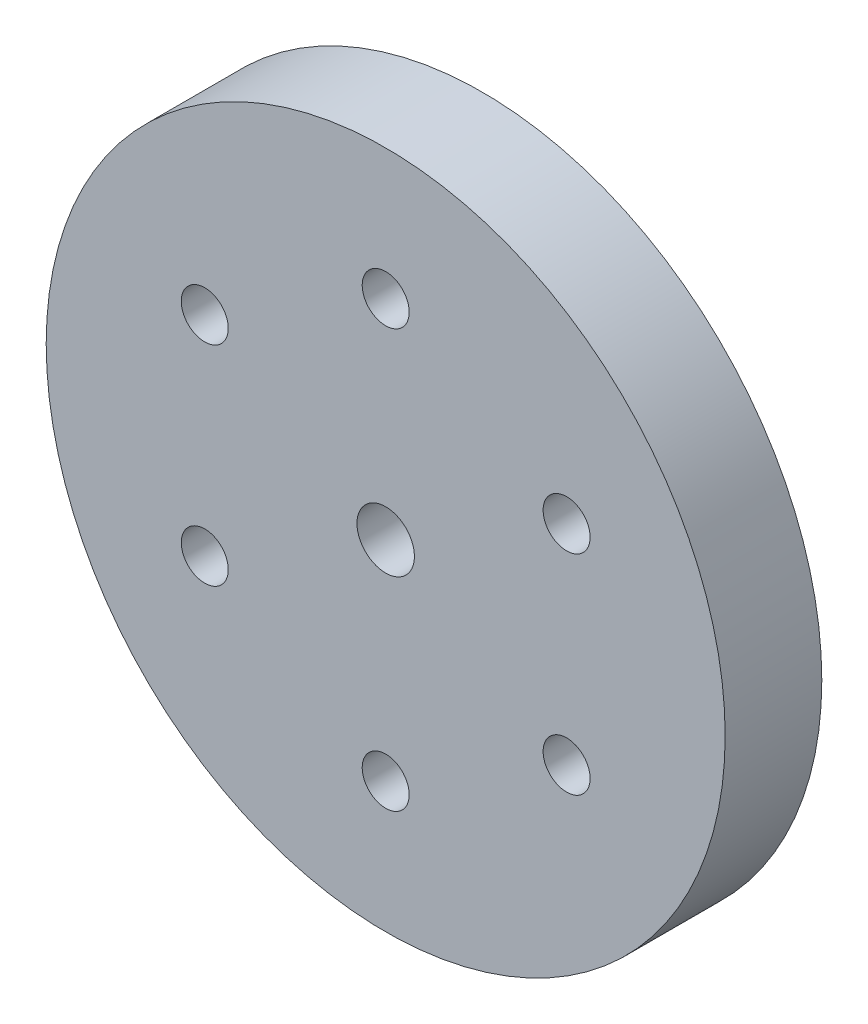
SolidWorks part; units mm, degrees
ref_plane "前视基准面" through (0, 0, 0) normal (0, 0, 1) x (1, 0, 0)
ref_plane "上视基准面" through (0, 0, 0) normal (0, 1, 0) x (1, 0, 0)
ref_plane "右视基准面" through (0, 0, 0) normal (1, 0, 0) x (0, 0, -1)
other "Configuration Table"
sketch "草图1" plane through (0, 0, 0) normal (0, 0, 1) x (1, 0, 0)
  circle A0 centre (0, 0) radius 13
  dimension "D1" = 26
extrude "凸台-拉伸1" add sketch "草图1" along normal blind 3.7 contours A0
sketch "草图2" plane through (0, 0, 0) normal (0, 0, -1) x (-1, 0, 0)
  circle A0 centre (0, 8) radius 1.5
  circle A1 centre (0, 8) radius 0.9
  dimension "D1" = 3
  dimension "D2" = 1.8
  dimension "D3" = 8
extrude "切除-拉伸1" cut sketch "草图2" against normal through all contours A1
extrude "切除-拉伸2" cut sketch "草图2<3>" against normal blind 1.5 contours A0
sketch "草图2<3>" plane through (0, 0, 0) normal (0, 0, -1) x (-1, 0, 0) same geometry as "草图2"
pattern_circular "阵列(圆周)1" count 6 over 360 about axis through (0, 0, 3.7) along (0, 0, -1) of "切除-拉伸1", "切除-拉伸2" reverse direction yes
sketch "草图3" plane through (0, 0, 0) normal (0, 0, -1) x (-1, 0, 0)
  circle A0 centre (0, 0) radius 2.55
  circle A1 centre (0, 0) radius 1.1
  dimension "D1" = 2.2
  dimension "D2" = 5.1
extrude "切除-拉伸3" cut sketch "草图3" against normal through all contours A1
